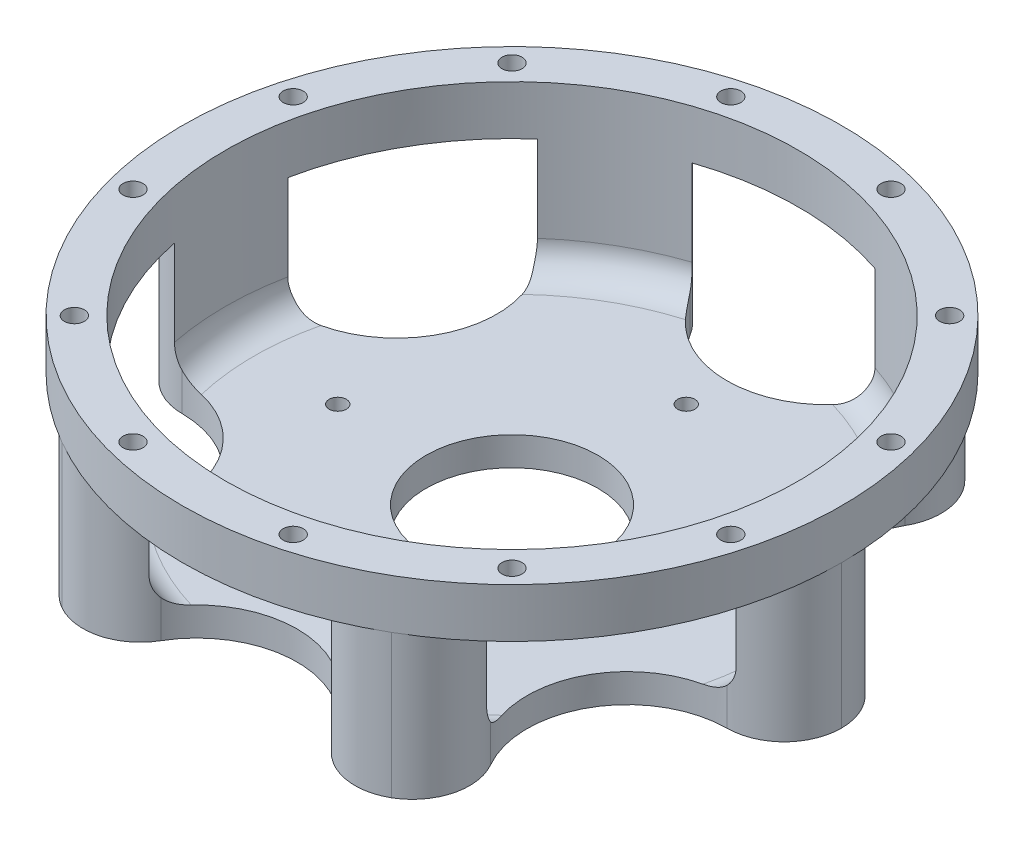
SolidWorks part; units mm, degrees
ref_plane "Front Plane" through (0, 0, 0) normal (0, 0, 1) x (1, 0, 0)
ref_plane "Top Plane" through (0, 0, 0) normal (0, 1, 0) x (1, 0, 0)
ref_plane "Right Plane" through (0, 0, 0) normal (1, 0, 0) x (0, 0, -1)
sketch "Sketch1" plane through (0, 0, 0) normal (0, 1, 0) x (1, 0, 0)
  circle A0 centre (0, 0) radius 57.5
  circle A1 centre (0, 0) radius 55 construction
  point P31 (0, 0)
  dimension "D1" = 115
  dimension "D2" = 110
extrude "Boss-Extrude1" add sketch "Sketch1" along normal blind 33.6
sketch "Sketch2" plane through (0, 33.6, 0) normal (0, 1, 0) x (1, 0, 0)
  circle A0 centre (0, 0) radius 50
  dimension "D1" = 100
extrude "Cut-Extrude1" cut sketch "Sketch2" against normal blind 28.6
sketch "Sketch7" plane through (0, 33.6, 0) normal (0, 1, 0) x (1, 0, 0)
  line L0 (-13.9762, 52.16) -> (0, 0) construction
  line L1 (0, 0) -> (13.9762, 52.16) construction
  line L2 (0, 62.0883) -> (0, -59.7095) construction
  circle A0 centre (0, 0) radius 54 construction
  circle A1 centre (-13.9762, 52.16) radius 1.75
  circle A2 centre (13.9762, 52.16) radius 1.75
  dimension "D1" = 108
  dimension "D4" = 3.5
  dimension "D2" = 15
  dimension "D3" = 15
extrude "Cut-Extrude4" cut sketch "Sketch7" against normal blind 10
fillet "Fillet2" radius 5 1 edges at (0, 5, 50)
sketch "Sketch3" plane through (0, 0, 0) normal (0, -1, 0) x (1, 0, 0)
  line L0 (0, 67.0594) -> (0, -18.0784) construction
  circle A0 centre (0, 0) radius 55 construction
  circle A1 centre (0, 55) radius 17.5
  dimension "D1" = 35
  dimension "D2" = 110
extrude "Cut-Extrude2" cut sketch "Sketch3" against normal blind 25
fillet "Fillet1" radius 10 2 edges at (-17.4985, 12.5, 54.7727) (17.4985, 12.5, 54.7727)
pattern_circular "CirPattern2" count 6 over 360 about axis through (0, 5, 0) along (0, 1, 0) of "Cut-Extrude2", "Fillet1" reverse direction yes
sketch "Sketch5" plane through (0, 0, 0) normal (0, -1, 0) x (1, 0, 0)
  line L0 (-30.4056, 0) -> (0, 30.4056) construction
  line L1 (-30.4056, 0) -> (0, -30.4056) construction
  line L2 (0, 30.4056) -> (30.4056, 0) construction
  line L3 (0, -30.4056) -> (30.4056, 0) construction
  circle A1 centre (0, 30.4056) radius 1.5
  circle A2 centre (30.4056, 0) radius 1.5
  circle A3 centre (0, -30.4056) radius 1.5
  circle A4 centre (-30.4056, 0) radius 1.5
  circle A5 centre (0, 0) radius 15
  point P1 (0, 0)
  point P6 (0, 35.3553)
  point P7 (0, 35.3553)
  point P14 (0, 0)
  dimension "D1" = 43
  dimension "D2" = 3
  dimension "D4" = 30
  dimension "D3" = 4
extrude "Cut-Extrude3" cut sketch "Sketch5" against normal blind 25
pattern_circular "CirPattern3" count 6 over 360 about axis through (0, 25, 0) along (0, -1, 0) of "Cut-Extrude4" reverse direction yes
